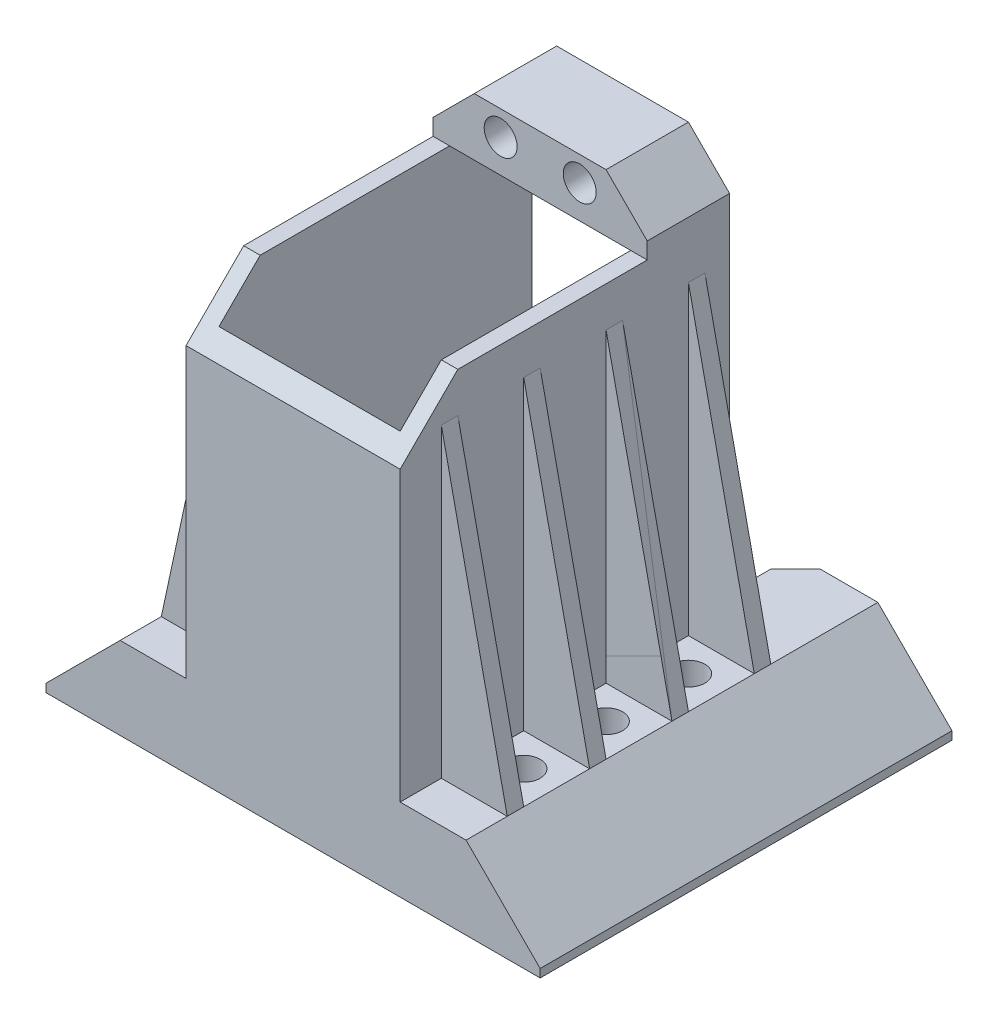
SolidWorks part; units mm, degrees
ref_plane "Front Plane" through (0, 0, 0) normal (0, 0, 1) x (1, 0, 0)
ref_plane "Top Plane" through (0, 0, 0) normal (0, 1, 0) x (1, 0, 0)
ref_plane "Right Plane" through (0, 0, 0) normal (1, 0, 0) x (0, 0, -1)
sketch "Sketch1" plane through (0, 0, 0) normal (0, 1, 0) x (1, 0, 0)
  line L1 (-30, 25) -> (30, 25)
  line L2 (-30, 25) -> (-30, -25)
  line L3 (-30, -25) -> (30, -25)
  line L4 (30, 25) -> (30, -25)
  line L5 (-30, 25) -> (30, -25) construction
  line L6 (-30, -25) -> (30, 25) construction
  point P0 (0, 0)
  dimension "D1" = 60
  dimension "D2" = 50
extrude "Boss-Extrude1" add sketch "Sketch1" along normal blind 10
chamfer "Chamfer1" distance 9 angle 45 2 edges at (30, 10, 0) (-30, 10, 0)
sketch "Sketch2" plane through (0, 10, 0) normal (0, 1, 0) x (1, 0, 0)
  line L0 (21, 25) -> (-21, 25) construction
  line L1 (-11, 35) -> (11, 35)
  line L2 (-11, 35) -> (-11, 15)
  line L3 (-11, 15) -> (11, 15)
  line L4 (11, 35) -> (11, 15)
  line L5 (-11, 35) -> (11, 15) construction
  line L6 (-11, 15) -> (11, 35) construction
  point P0 (0, 25)
  dimension "D1" = 22
  dimension "D2" = 20
extrude "Cut-Extrude1" cut sketch "Sketch2" against normal through all
chamfer "Chamfer2" distance 3 angle 45 2 edges at (-11, 5, -25) (11, 5, -25)
sketch "Sketch3" plane through (0, 0, -15) normal (0, 0, -1) x (-1, 0, 0)
  line L0 (4.8, 5) -> (-4.8, 5) construction
  line L1 (0, 0) -> (0, 5) construction
  circle A0 centre (-4.8, 5) radius 2
  circle A1 centre (4.8, 5) radius 2
  dimension "D1" = 4
  dimension "D2" = 4
  dimension "D3" = 5
  dimension "D4" = 9.6
extrude "Cut-Extrude2" cut sketch "Sketch3" against normal blind 10
sketch "Sketch4" plane through (0, 10, 0) normal (0, 1, 0) x (1, 0, 0)
  line L0 (-21, -25) -> (21, -25) construction
  line L1 (-11, 15) -> (-13, 15)
  line L2 (-11, 15) -> (-11, -23)
  line L3 (-11, -25) -> (-13, -25)
  line L4 (-13, 15) -> (-13, -25)
  line L6 (11, 15) -> (13, 15)
  line L7 (11, 15) -> (11, -23)
  line L8 (11, -25) -> (13, -25)
  line L9 (13, 15) -> (13, -25)
  line L10 (-11, -25) -> (11, -25)
  line L12 (-11, -23) -> (11, -23)
  dimension "D1" = 2
  dimension "D2" = 2
  dimension "D3" = 2
extrude "Boss-Extrude2" add sketch "Sketch4" along normal blind 42
sketch "Sketch5" plane through (0, 0, 0) normal (0, 0, 1) x (1, 0, 0)
  line L0 (21, 10) -> (13, 10)
  line L1 (13, 10) -> (13, 47.1392)
  line L3 (13, 47.1392) -> (21, 10)
  line L4 (13, 52) -> (13, 10) construction
  line L5 (-21, 10) -> (-13, 10)
  line L6 (-13, 10) -> (-13, 47.1392)
  line L7 (-13, 52) -> (-13, 10) construction
  line L8 (-13, 47.1392) -> (-21, 10)
extrude "Boss-Extrude3" add sketch "Sketch5" against normal blind 2 separate body
pattern_linear "LPattern1" count 3 spacing 10 along (0, 0, 1) count 2 spacing 10 along (0, 0, -1) of "Boss-Extrude3"
sketch "Sketch6" plane through (0, 52, 0) normal (0, 1, 0) x (1, 0, 0)
  line L0 (13, -25) -> (13, 15) construction
  line L1 (-13, 15) -> (13, 15)
  line L2 (-13, 15) -> (-13, 5)
  line L3 (-13, 5) -> (13, 5)
  line L4 (13, 15) -> (13, 5)
  dimension "D1" = 10
extrude "Boss-Extrude4" add sketch "Sketch6" along normal blind 7
sketch "Sketch7" plane through (0, 59, 0) normal (0, 1, 0) x (1, 0, 0)
  line L0 (13, 5) -> (13, 15) construction
  line L1 (-13, 15) -> (13, 15)
  line L2 (-13, 15) -> (-13, 13)
  line L3 (-13, 13) -> (13, 13)
  line L4 (13, 15) -> (13, 13)
  dimension "D1" = 2
chamfer "Chamfer5" distance 7 angle 45 1 edges at (0, 52, 25)
sketch "Sketch10" plane through (0, 0, -15) normal (0, 0, -1) x (-1, 0, 0)
  line L0 (-4.8, 56) -> (4.8, 56) construction
  line L1 (0, 56) -> (0, 52) construction
  line L2 (-11, 52) -> (11, 52) construction
  circle A0 centre (-4.8, 56) radius 2
  circle A1 centre (4.8, 56) radius 2
  dimension "D1" = 4
  dimension "D2" = 4
  dimension "D3" = 4
  dimension "D4" = 9.6
extrude "Cut-Extrude4" cut sketch "Sketch10" against normal through all
chamfer "Chamfer6" distance 5 angle 45 2 edges at (13, 59, -10) (-13, 59, -10)
sketch "Sketch11" plane through (0, 10, 0) normal (0, 1, 0) x (1, 0, 0)
  line L0 (-17, -14) -> (-17, -25) construction
  line L1 (-21, -25) -> (-13, -25) construction
  circle A0 centre (-17, -14) radius 2
  dimension "D2" = 4
  dimension "D1" = 11
extrude "Cut-Extrude5" cut sketch "Sketch11" against normal through all
mirror "Mirror4" about plane through (0, 0, 0) normal (1, 0, 0) of "Cut-Extrude5"
pattern_linear "LPattern2" count 3 spacing 10 along (0, 0, -1) of "Mirror4"
